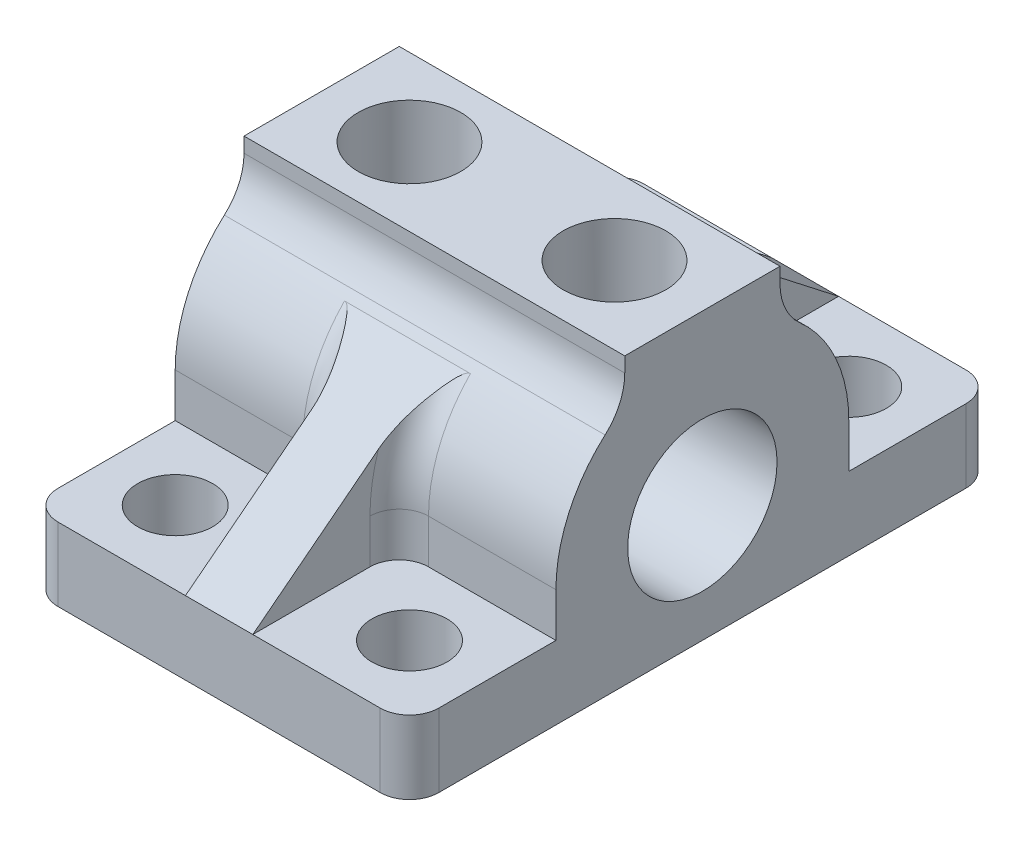
SolidWorks part; units mm, degrees
material "PLA2"
ref_plane "Front Plane" through (0, 0, 0) normal (0, 0, 1) x (1, 0, 0)
ref_plane "Top Plane" through (0, 0, 0) normal (0, 1, 0) x (1, 0, 0)
ref_plane "Right Plane" through (0, 0, 0) normal (1, 0, 0) x (0, 0, -1)
sketch "Sketch1" plane through (0, 0, 0) normal (1, 0, 0) x (0, 0, -1)
  line L0 (0, 0) -> (27506.0917, 0) construction
  line L1 (0.3138, 24.13) -> (27506.4055, 24.13) construction
  line L2 (0, 29.21) -> (0, 0) construction
  line L3 (12.7, 24.13) -> (-12.7, 24.13)
  line L4 (-12.7, 24.13) -> (-12.7, 27.305)
  line L5 (-12.7, 27.305) -> (-6.35, 27.305)
  line L6 (-6.35, 27.305) -> (-6.35, 29.21)
  line L7 (0, 29.21) -> (0, 35.56) construction
  line L8 (6.35, 27.305) -> (6.35, 29.21)
  line L9 (12.7, 27.305) -> (6.35, 27.305)
  line L10 (12.7, 24.13) -> (12.7, 27.305)
  circle A0 centre (0, 29.21) radius 3.2385
  arc A1 (6.35, 29.21) -> (-6.35, 29.21) centre (0, 29.21) ccw
  point P19 (0, 24.13)
  dimension "D2" = 6.477
  dimension "D4" = 12.7
  dimension "D7" = 3.1115
  dimension "D1" = 24.13
  dimension "D3" = 29.21
  dimension "D5" = 3.175
  dimension "D6" = 6.35
extrude "Boss-Extrude1" add sketch "Sketch1" along normal mid plane 16.51
sketch "Sketch2" plane through (0, 0, 0) normal (1, 0, 0) x (0, 0, -1)
  line L0 (0, 32.4485) -> (0, 25.9715) construction
  line L1 (-4.5348, 33.655) -> (-12.7, 27.305)
  line L2 (-6.35, 27.305) -> (-12.7, 27.305) construction
  line L3 (-12.7, 27.305) -> (-4.5348, 27.305)
  line L4 (-4.5348, 27.305) -> (-4.5348, 33.655)
  line L5 (4.5348, 27.305) -> (4.5348, 33.655)
  line L6 (12.7, 27.305) -> (4.5348, 27.305)
  line L7 (4.5348, 33.655) -> (12.7, 27.305)
  circle A0 centre (0, 29.21) radius 3.2385 construction
  arc A1 (6.35, 29.21) -> (-6.35, 29.21) centre (0, 29.21) ccw construction
  point P12 (-6.0575, 27.305)
  dimension "D1" = 6.35
extrude "Boss-Extrude2" add sketch "Sketch2" along normal mid plane 2.921
sketch "Sketch3" plane through (0, 27.305, 0) normal (0, 1, 0) x (1, 0, 0)
  line L0 (-8.255, 0) -> (8.255, 0) construction
  line L1 (-8.255, 6.35) -> (-8.255, -6.35) construction
  line L2 (8.255, -6.35) -> (8.255, 6.35) construction
  line L3 (0, 12.7) -> (0, -12.7) construction
  line L4 (1.4605, 12.7) -> (-1.4605, 12.7) construction
  line L5 (1.4605, -12.7) -> (-1.4605, -12.7) construction
  circle A0 centre (-5.08, 9.525) radius 1.6256
  circle A1 centre (5.08, 9.525) radius 1.6256
  circle A2 centre (5.08, -9.525) radius 1.6256
  circle A3 centre (-5.08, -9.525) radius 1.6256
  dimension "D1" = 3.2512
  dimension "D2" = 10.16
  dimension "D3" = 19.05
extrude "Cut-Extrude1" cut sketch "Sketch3" against normal through all
sketch "Sketch4" plane through (8.255, 0, 0) normal (1, 0, 0) x (0, 0, -1)
  line L0 (3.3655, 34.5948) -> (-3.3655, 34.5948)
  arc A0 (6.35, 29.21) -> (-6.35, 29.21) centre (0, 29.21) ccw construction
  arc A1 (3.3655, 34.5948) -> (-3.3655, 34.5948) centre (0, 29.21) ccw
  dimension "D1" = 6.731
extrude "Cut-Extrude2" cut sketch "Sketch4" against normal through all
sketch "Sketch6" plane through (0, 34.5948, 0) normal (0, 1, 0) x (1, 0, 0)
  line L4 (8.255, -3.3655) -> (8.255, 3.3655)
  line L5 (8.255, 3.3655) -> (-8.255, 3.3655)
  line L6 (-8.255, 3.3655) -> (-8.255, -3.3655)
  line L7 (-8.255, -3.3655) -> (8.255, -3.3655)
  line L8 (8.255, -3.3655) -> (8.255, 3.3655)
  line L9 (8.255, 3.3655) -> (-8.255, 3.3655)
  line L10 (-8.255, 3.3655) -> (-8.255, -3.3655)
  line L11 (-8.255, -3.3655) -> (8.255, -3.3655)
  dimension "D1" = 0
extrude "Boss-Extrude3" add sketch "Sketch6" along normal blind 1.905
sketch "Sketch5" plane through (0, 36.4998, 0) normal (0, 1, 0) x (1, 0, 0)
  line L0 (0, 12.7) -> (0, -12.7) construction
  line L1 (1.4605, 12.7) -> (-1.4605, 12.7) construction
  line L2 (1.4605, -12.7) -> (-1.4605, -12.7) construction
  line L3 (-8.255, 0) -> (8.255, 0) construction
  line L6 (-8.255, 3.3655) -> (-8.255, -3.3655) construction
  line L7 (8.255, -3.3655) -> (8.255, 3.3655) construction
  circle A0 centre (-4.445, 0) radius 2.2225
  circle A1 centre (4.445, 0) radius 2.2225
  point P8 (0, 0)
  point P11 (0, 0)
  point P16 (0, 0)
  dimension "D1" = 4.445
  dimension "D2" = 8.89
extrude "Cut-Extrude3" cut sketch "Sketch5" against normal blind 6.35
fillet "Fillet1" radius 1.27 12 edges at (-1.4605, 31.6107, 5.8787) (1.4605, 31.6107, 5.8787) (-1.4605, 31.6107, -5.8787) (1.4605, 31.6107, -5.8787) (-1.4605, 28.2575, 6.35) (1.4605, 28.2575, 6.35) (-1.4605, 28.2575, -6.35) (1.4605, 28.2575, -6.35) (-8.255, 25.7175, -12.7) (8.255, 25.7175, -12.7) (-8.255, 25.7175, 12.7) (8.255, 25.7175, 12.7)
fillet "Fillet2" radius 2.54 2 edges at (0, 34.5948, -3.3655) (0, 34.5948, 3.3655)
